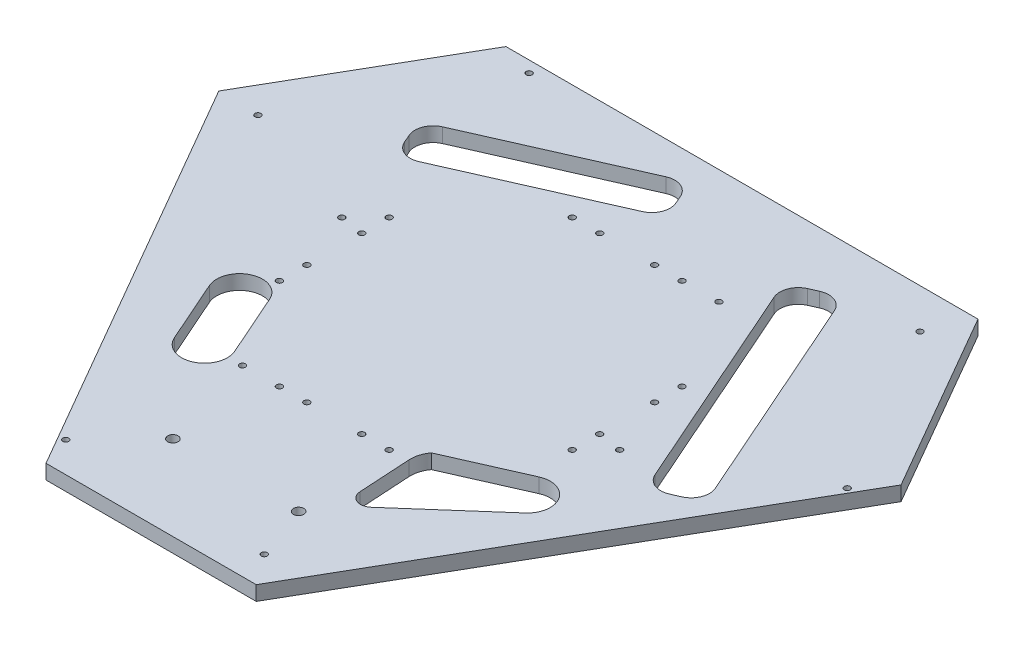
SolidWorks part; units mm, degrees
material "Pin"
ref_plane "Plan de face" through (0, 0, 0) normal (0, 0, 1) x (1, 0, 0)
ref_plane "Plan de dessus" through (0, 0, 0) normal (0, 1, 0) x (1, 0, 0)
ref_plane "Plan de droite" through (0, 0, 0) normal (1, 0, 0) x (0, 0, -1)
sketch "BB_position" plane through (0, 0, 0) normal (0, 1, 0) x (1, 0, 0)
  line L0 (-110, 63.5085) -> (110, 63.5085) construction
  line L7 (110, 63.5085) -> (0, -127.0171) construction
  line L8 (0, -127.0171) -> (-110, 63.5085) construction
  circle A0 centre (0, 0) radius 127.0171 construction
  circle A1 centre (-110, 63.5085) radius 5 construction
  circle A2 centre (110, 63.5085) radius 5 construction
  circle A3 centre (0, -127.0171) radius 5 construction
  dimension "D1" = 220
  dimension "D2" = 10
sketch "BB_Footprint" plane through (0, 0, 0) normal (0, 1, 0) x (1, 0, 0)
  line L0 (-110, 63.5085) -> (-128.115, 32.1324) construction
  line L1 (-128.115, 32.1324) -> (-131.4232, 34.0424) construction
  line L2 (-131.4232, 34.0424) -> (-88.0354, 109.1924) construction
  line L3 (95.1932, 96.7946) -> (138.5811, 21.6447) construction
  line L4 (110, 63.5085) -> (91.885, 94.8846) construction
  line L5 (91.885, 94.8846) -> (95.1932, 96.7946) construction
  line L6 (36.23, -130.8371) -> (-50.5457, -130.8371) construction
  line L7 (0, -127.0171) -> (36.23, -127.0171) construction
  line L8 (36.23, -127.0171) -> (36.23, -130.8371) construction
  circle A0 centre (-110, 63.5085) radius 5 construction
  circle A1 centre (0, 0) radius 127.0171 construction
  circle A2 centre (-110, 63.5085) radius 5 construction
  circle A3 centre (110, 63.5085) radius 5 construction
  circle A4 centre (0, -127.0171) radius 5 construction
  point P23 (0, 0)
  dimension "D1" = 3.82
  dimension "D2" = 36.23
  dimension "D3" = 86.7757
  dimension "D4" = 3
sketch "Esquisse3" plane through (0, 0, 0) normal (0, 1, 0) x (1, 0, 0)
  line L0 (-103.1624, 114.1924) -> (103.1624, 114.1924)
  line L1 (-103.1624, 114.1924) -> (-149.104, 34.6191)
  line L2 (-149.104, 34.6191) -> (-45.9416, -144.0633)
  line L3 (-45.9416, -144.0633) -> (45.9416, -144.0633)
  line L4 (45.9416, -144.0633) -> (149.104, 34.6191)
  line L5 (149.104, 34.6191) -> (103.1624, 114.1924)
  line L6 (-131.4232, 34.0424) -> (-88.0354, 109.1924) construction
  point P2 (0, 114.1924)
  point P7 (0, -144.0633)
  dimension "D1" = 5
sketch "TB_boltPattern" plane through (0, 0, 0) normal (0, 1, 0) x (1, 0, 0)
  line L0 (0, 143.3581) -> (0, -141.7362) construction
  line L1 (-23, 57.7) -> (-13, 57.7) construction
  line L2 (-23, 57.7) -> (-23, 43.7) construction
  line L3 (-23, 43.7) -> (-13, 43.7) construction
  line L4 (-13, 57.7) -> (-13, 43.7) construction
  line L5 (-57.7, 23) -> (-43.7, 23) construction
  line L6 (-57.7, 23) -> (-57.7, 13) construction
  line L7 (-57.7, 13) -> (-43.7, 13) construction
  line L8 (-43.7, 23) -> (-43.7, 13) construction
  line L9 (-204.4729, 0) -> (279.6048, 0) construction
  circle A0 centre (-24, 64) radius 1.6 construction
  circle A1 centre (-12, 64) radius 1.6 construction
  circle A2 centre (-64, 24) radius 1.6 construction
  circle A3 centre (-64, 12) radius 1.6 construction
  point P8 (-18, 57.7)
  dimension "D5" = 3.2
  dimension "D10" = 6.3
  dimension "D1" = 12
  dimension "D2" = 12
  dimension "D3" = 40
  dimension "D4" = 40
  dimension "D6" = 14
  dimension "D7" = 10
  dimension "D8" = 1
  dimension "D9" = 6.3
  dimension "D11" = 1
  dimension "D12" = 12
  dimension "D13" = 12
extrude "Boss.-Extru.1" add sketch "Esquisse3" against normal blind 6.35
hole_wizard "BBCase_boltPattern" positions "Esquisse6" profile "Esquisse8" hole size "M3" standard "Ansi Metric"
sketch "Esquisse6" plane through (0, 0, 0) normal (0, 1, 0) x (1, 0, 0)
  point P0 (-88.0354, 109.1924)
  point P3 (-131.4232, 34.0424)
sketch "Esquisse8" plane through (-88.0354, 0, -109.1924) normal (1, 0, 0) x (0, 0, 1)
  line L0 (0, 0) -> (0, 7.1311)
  line L1 (0, 7.1311) -> (1.3, 6.35)
  line L2 (1.3, 6.35) -> (1.3, 0)
  line L5 (1.3, 0) -> (0, 0)
  line L10 (0, 7.1311) -> (-1.3, 6.35) construction
  line L11 (0, -6.35) -> (0, 107.95) construction
  dimension "Diamètre du perçage" = 2.6
  dimension "Profondeur du perçage" = 6.35
  dimension "Angle de pointe" = 118
ref_axis "Axe1" through (0, 0, 0) along (0, 1, 0)
pattern_circular "Répétition circulaire1" count 3 over 360 about axis through (0, 0, 0) along (0, 1, 0) of "BBCase_boltPattern"
hole_wizard "Dégagement M32" positions "Esquisse9" profile "Esquisse10" hole size "M3" standard "Ansi Metric"
sketch "Esquisse9" plane through (0, 0, 0) normal (0, 1, 0) x (1, 0, 0)
  point P0 (-24, 64)
  point P3 (-12, 64)
  point P6 (-64, 24)
  point P9 (-64, 12)
sketch "Esquisse10" plane through (-24, 0, -64) normal (1, 0, 0) x (0, 0, 1)
  line L0 (0, 0) -> (0, 7.1311)
  line L1 (0, 7.1311) -> (1.3, 6.35)
  line L2 (1.3, 6.35) -> (1.3, 0)
  line L5 (1.3, 0) -> (0, 0)
  line L10 (0, 7.1311) -> (-1.3, 6.35) construction
  line L11 (0, -6.35) -> (0, 107.95) construction
  dimension "Diamètre du perçage" = 2.6
  dimension "Profondeur du perçage" = 6.35
  dimension "Angle de pointe" = 118
pattern_circular "Répétition circulaire2" count 4 over 360 about axis through (0, 0, 0) along (0, 1, 0) of "Dégagement M32"
sketch "HB_Footprint" plane through (0, 0, 0) normal (0, 1, 0) x (1, 0, 0)
  line L0 (-74.3426, 13.6262) -> (40.0015, 64.1278) construction
  line L1 (40.0015, 64.1278) -> (74.3426, -13.6262) construction
  line L2 (-74.3426, 13.6262) -> (-40.0015, -64.1278) construction
  line L3 (-40.0015, -64.1278) -> (74.3426, -13.6262) construction
  line L8 (-77.8072, 30.1336) -> (-30.1336, -77.8072) construction
  line L9 (-30.1336, -77.8072) -> (77.8072, -30.1336) construction
  line L10 (77.8072, -30.1336) -> (30.1336, 77.8072) construction
  line L11 (-77.8072, 30.1336) -> (30.1336, 77.8072) construction
  line L12 (-23.8368, 53.9704) -> (23.8368, -53.9704) construction
  line L13 (-57.1721, -25.2508) -> (0, 0) construction
  circle A0 centre (-74.3426, 13.6262) radius 1.6 construction
  circle A1 centre (40.0015, 64.1278) radius 1.6 construction
  circle A2 centre (-40.0015, -64.1278) radius 1.6 construction
  circle A3 centre (74.3426, -13.6262) radius 1.6 construction
  point P10 (23.8368, -53.9704)
  point P19 (-17.1706, 38.877)
  dimension "D4" = 3.2
  dimension "D1" = 125
  dimension "D2" = 85
  dimension "D3" = 118
hole_wizard "Dégagement M33" positions "Esquisse11" profile "Esquisse12" hole size "M3" standard "Ansi Metric"
sketch "Esquisse11" plane through (0, 0, 0) normal (0, 1, 0) x (1, 0, 0)
  point P0 (-74.3426, 13.6262)
  point P3 (-40.0015, -64.1278)
  point P6 (74.3426, -13.6262)
  point P9 (40.0015, 64.1278)
sketch "Esquisse12" plane through (-74.3426, 0, -13.6262) normal (1, 0, 0) x (0, 0, 1)
  line L0 (0, 0) -> (0, 7.1311)
  line L1 (0, 7.1311) -> (1.3, 6.35)
  line L2 (1.3, 6.35) -> (1.3, 0)
  line L5 (1.3, 0) -> (0, 0)
  line L10 (0, 7.1311) -> (-1.3, 6.35) construction
  line L11 (0, -6.35) -> (0, 107.95) construction
  dimension "Diamètre du perçage" = 2.6
  dimension "Profondeur du perçage" = 6.35
  dimension "Angle de pointe" = 118
sketch "Esquisse13" plane through (0, 0, 0) normal (0, 1, 0) x (1, 0, 0)
  line L0 (113.0252, -14.5791) -> (94.7302, -22.6594)
  line L1 (94.7302, -22.6594) -> (47.0566, 85.2815)
  line L2 (47.0566, 85.2815) -> (65.3516, 93.3617)
  line L3 (65.3516, 93.3617) -> (113.0252, -14.5791)
  line L5 (-77.8072, 30.1336) -> (30.1336, 77.8072) construction
  line L7 (40.0015, 64.1278) -> (74.3426, -13.6262) construction
  line L13 (-30.1336, -77.8072) -> (77.8072, -30.1336) construction
  line L14 (-11.64, 103.085) -> (-93.9678, 66.7238)
  line L15 (-93.9678, 66.7238) -> (-85.8875, 48.4287)
  line L16 (-85.8875, 48.4287) -> (-3.5597, 84.7899)
  line L17 (-3.5597, 84.7899) -> (-11.64, 103.085)
  line L18 (-77.8072, 30.1336) -> (-30.1336, -77.8072) construction
  dimension "D1" = 15
  dimension "D2" = 20
  dimension "D5" = 20
  dimension "D6" = 90
  dimension "D7" = 20
extrude "Enlèv. mat.-Extru.1" cut sketch "Esquisse13" against normal up to surface (6.35 mm away) up to face at (-74.3426, -6.35, -12.3262)
sketch "Esquisse15" plane through (0, 0, 0) normal (0, 1, 0) x (1, 0, 0)
  line L0 (-27.48, -107.0633) -> (27.48, -107.0633) construction
  line L1 (0, 200143.3581) -> (0, -200141.7362) construction
  line L2 (-45.9416, -144.0633) -> (45.9416, -144.0633) construction
  circle A0 centre (-27.48, -107.0633) radius 3.5746 construction
  circle A1 centre (27.48, -107.0633) radius 3.5746 construction
  point P4 (0, -107.0633)
  dimension "D1" = 54.96
  dimension "D2" = 37
hole_wizard "Dégagement M51" positions "Esquisse16" profile "Esquisse17" hole size "M5" standard "Ansi Metric"
sketch "Esquisse16" plane through (0, 0, 0) normal (0, 1, 0) x (1, 0, 0)
  point P0 (-27.48, -107.0633)
  point P3 (27.48, -107.0633)
sketch "Esquisse17" plane through (-27.48, 0, 107.0633) normal (1, 0, 0) x (0, 0, 1)
  line L0 (0, 0) -> (0, 7.714)
  line L1 (0, 7.714) -> (2.27, 6.35)
  line L2 (2.27, 6.35) -> (2.27, 0)
  line L5 (2.27, 0) -> (0, 0)
  line L10 (0, 7.714) -> (-2.27, 6.35) construction
  line L11 (0, -6.35) -> (0, 107.95) construction
  dimension "Diamètre du perçage" = 4.54
  dimension "Profondeur du perçage" = 6.35
  dimension "Angle de pointe" = 118
sketch "Esquisse18" plane through (0, 0, 0) normal (0, 1, 0) x (1, 0, 0)
  line L0 (71.0075, -50.6279) -> (43.5649, -62.7483) construction
  line L2 (66.9674, -41.4803) -> (34.336, -55.8925)
  line L3 (-30.1336, -77.8072) -> (77.8072, -30.1336) construction
  line L4 (23.8368, -53.9704) -> (77.8072, -30.1336) construction
  line L5 (50.822, -42.052) -> (57.2862, -56.6881) construction
  line L6 (-68.3683, -37.0282) -> (-56.2479, -64.4708) construction
  line L7 (-59.2207, -32.9881) -> (-47.1003, -60.4307)
  line L8 (-77.5158, -41.0684) -> (-65.3954, -68.511)
  line L9 (-74.3426, 13.6262) -> (-40.0015, -64.1278) construction
  line L10 (-57.1721, -25.2508) -> (-40.0015, -64.1278) construction
  line L11 (-48.5868, -44.6893) -> (-62.3081, -50.7495) construction
  line L12 (32.0883, -63.4284) -> (33.4385, -86.2128)
  line L13 (41.7305, -89.6726) -> (77.6091, -58.1391)
  arc A0 (77.6091, -58.1391) -> (66.9674, -41.4803) centre (71.0075, -50.6279) ccw
  arc A1 (34.336, -55.8925) -> (32.0883, -63.4284) centre (43.5649, -62.7483) ccw
  arc A2 (-59.2207, -32.9881) -> (-77.5158, -41.0684) centre (-68.3683, -37.0282) ccw
  arc A3 (-65.3954, -68.511) -> (-47.1003, -60.4307) centre (-56.2479, -64.4708) ccw
  arc A4 (33.4385, -86.2128) -> (41.7305, -89.6726) centre (38.4297, -85.917) ccw
  point P2 (57.2862, -56.6881)
  point P16 (-62.3081, -50.7495)
  point P35 (34.0438, -96.4284)
  dimension "D4" = 15
  dimension "D6" = 10
  dimension "D1" = 10
  dimension "D11" = 5
  dimension "D2" = 6
  dimension "D3" = 30
  dimension "D5" = 30
  dimension "D7" = 35
  dimension "D8" = 58
  dimension "D9" = 10
  dimension "D10" = 33
extrude "Enlèv. mat.-Extru.3" cut sketch "Esquisse18" against normal up to surface (6.35 mm away) up to face at (-27.48, -6.35, 109.3333)
fillet "Congé1" radius 8 8 edges at (47.0566, -3.175, -85.2815) (65.3516, -3.175, -93.3617) (113.0252, -3.175, 14.5791) (94.7302, -3.175, 22.6594) (-11.64, -3.175, -103.085) (-3.5597, -3.175, -84.7899) (-85.8875, -3.175, -48.4287) (-93.9678, -3.175, -66.7238)
